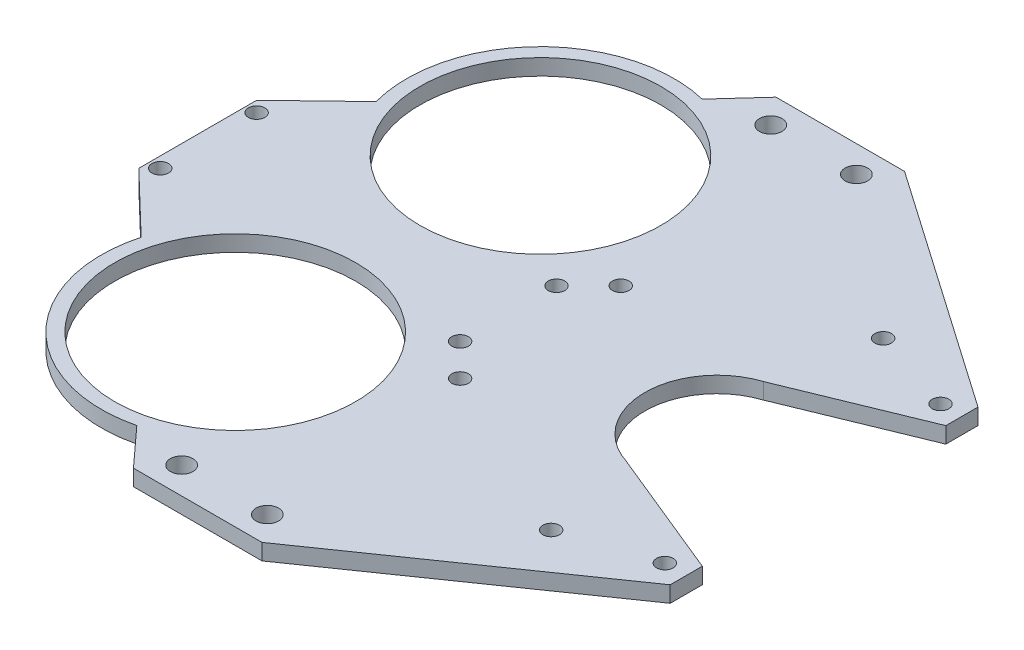
SolidWorks part; units mm, degrees
ref_plane "前视基准面" through (0, 0, 0) normal (0, 0, 1) x (1, 0, 0)
ref_plane "上视基准面" through (0, 0, 0) normal (0, 1, 0) x (1, 0, 0)
ref_plane "右视基准面" through (0, 0, 0) normal (1, 0, 0) x (0, 0, -1)
sketch "草图1" plane through (0, 0, 0) normal (0, 1, 0) x (1, 0, 0)
  line L0 (-55, 11) -> (-55, -11)
  line L1 (-55, 0) -> (5.5, 0) construction
  line L2 (-19.5, 28.5) -> (-19.5, -28.5) construction
  line L3 (-55, -11) -> (-27.8194, -37.148)
  line L4 (28.5, 0) -> (83.1006, 0) construction
  line L5 (-55, 11) -> (-27.8194, 37.148)
  line L6 (14, 12.5399) -> (14, 16.5)
  line L7 (-19.5, 40.5) -> (45.0428, 34.8675)
  line L8 (19, 21.5) -> (69.6179, 21.5)
  line L9 (14, -12.5399) -> (14, -16.5)
  line L13 (19, -21.5) -> (69.6179, -21.5)
  line L15 (-19.5, -40.5) -> (45.0428, -34.8675)
  circle A0 centre (0, 0) radius 1.55
  circle A1 centre (-27.5, 0) radius 1.55
  circle A2 centre (-46.5, 0) radius 1.55
  circle A3 centre (-19.5, -28.5) radius 4
  circle A4 centre (-19.5, -28.5) radius 8 construction
  circle A5 centre (-19.5, -28.5) radius 9.5 construction
  circle A6 centre (-19.5, -20.5) radius 1.55
  circle A7 centre (-19.5, -36.5) radius 1.55
  circle A8 centre (-10, -28.5) radius 1.55
  circle A9 centre (-29, -28.5) radius 1.55
  circle A10 centre (-29, 28.5) radius 1.55
  circle A11 centre (-10, 28.5) radius 1.55
  circle A12 centre (-19.5, 36.5) radius 1.55
  circle A13 centre (-19.5, 20.5) radius 1.55
  circle A14 centre (-19.5, 28.5) radius 4
  arc A15 (-27.8194, -37.148) -> (-17.4214, -40.3186) centre (-19.5, -28.5) ccw
  arc A16 (45.0428, -34.8675) -> (69.6179, -21.5) centre (42, 0) ccw
  arc A17 (-27.8194, 37.148) -> (-17.4214, 40.3186) centre (-19.5, 28.5) cw
  arc A18 (14, 16.5) -> (19, 21.5) centre (19, 16.5) cw
  arc A19 (45.0428, 34.8675) -> (69.6179, 21.5) centre (42, 0) cw
  arc A22 (14, 12.5399) -> (14, -12.5399) centre (19, 0) ccw
  arc A23 (14, -16.5) -> (19, -21.5) centre (19, -16.5) ccw
  point P10 (-55, 0)
  point P15 (-19.5, 0)
  dimension "D1" = 3.1
  dimension "D2" = 3.1
  dimension "D3" = 3.1
  dimension "D9" = 19
  dimension "D10" = 16
  dimension "D11" = 8
  dimension "D12" = 3.1
  dimension "D13" = 3.1
  dimension "D14" = 3.1
  dimension "D15" = 3.1
  dimension "D16" = 24
  dimension "D18" = 70
  dimension "D4" = 27.5
  dimension "D5" = 19
  dimension "D6" = 8.5
  dimension "D7" = 19.5
  dimension "D8" = 57
  dimension "D17" = 22
  dimension "D19" = 42
extrude "凸台-拉伸1" add sketch "草图1" along normal blind 3 contours A23 L9 A22 L6 A18 L8 A19 L7 A17 L5 L0 L3 A15 L15 A16 L13 A13 A11 A0 A1 A2 A3 A6 A7 A8 A9 A10 A12 A14 region at (-3.8495, 0, 0)
sketch "草图2" plane through (0, 3, 0) normal (0, 1, 0) x (1, 0, 0)
  line L0 (0, 0) -> (23.4042, 0) construction
  line L1 (5, 38.3619) -> (5, 57.5706) construction
  line L2 (-16.1256, 50) -> (-7, 50) construction
  line L3 (-7, 60) -> (-28.364, 36.5889)
  line L4 (17, 60) -> (-7, 60)
  line L5 (17, 60) -> (17, 50)
  line L6 (-17.4214, 40.3186) -> (-19.6569, 39.1776)
  line L7 (-19.6569, 39.1776) -> (-24.7059, 39.3119)
  line L8 (17, 60) -> (-7, 50) construction
  line L9 (17, 50) -> (-7, 60) construction
  line L10 (17, 37.3147) -> (17, 50)
  line L11 (-19.5, 40.5) -> (45.0428, 34.8675) construction
  line L12 (-17.4214, 40.3186) -> (17, 37.3147)
  line L13 (-3, 55) -> (13, 55) construction
  arc A1 (-24.7059, 39.3119) -> (-28.364, 36.5889) centre (-19.5, 28.5) ccw
  circle A2 centre (13, 55) radius 2.1
  circle A3 centre (-3, 55) radius 2.1
  point P10 (5, 55)
  dimension "D5" = 4.2
  dimension "D6" = 4.2
  dimension "D9" = 4
  dimension "D1" = 5
  dimension "D3" = 24
  dimension "D4" = 10
extrude "凸台-拉伸3" add sketch "草图2" against normal blind 3
fillet "圆角1" radius 4 1 edges at (17, 1.5, -37.3147)
fillet "圆角2" radius 314 1 edges at (-28.1008, 1.5, -36.8773) type face fillet first side face at (-41.5504, 1.5, -23.9386) second side face at (-17.5504, 1.5, -48.4386)
mirror "镜向2" about plane through (0, 0, 0) normal (0, 0, 1) of "凸台-拉伸3"
fillet "圆角3" radius 314 1 edges at (-28.1008, 1.5, 36.8773) type face fillet first side face at (-41.5504, 1.5, 23.9386) second side face at (-17.5504, 1.5, 48.4386)
fillet "圆角4" radius 4 1 edges at (17, 1.5, 37.3147)
sketch "草图3" plane through (0, 0, 0) normal (0, -1, 0) x (1, 0, 0)
  line L0 (-19.5, 28.5) -> (-10.1874, 19.4294) construction
  arc A1 (-8.6867, 48.2313) -> (-38.9114, 17.1226) centre (-19.5, 28.5) ccw
  arc A8 (-38.9114, 17.1226) -> (-30.7155, 21.9264) centre (-34.8135, 19.5245) ccw
  arc A9 (-13.2523, 39.9003) -> (-8.6867, 48.2313) centre (-10.9695, 44.0658) ccw
  arc A13 (-13.2523, 39.9003) -> (-30.7155, 21.9264) centre (-19.5, 28.5) ccw
  point P16 (-19.5, 28.5)
extrude "切除-拉伸2" cut sketch "草图3" against normal blind 3
sketch "草图4" plane through (0, 0, 0) normal (0, -1, 0) x (1, 0, 0)
  line L0 (-43.6248, 21.943) -> (-41.5357, 23.9528)
  line L1 (-55, 11) -> (-41.5357, 23.9528) construction
  line L2 (-15.5344, 50.6478) -> (-13.5804, 52.7891)
  line L3 (-7, 60) -> (-15.5344, 50.6478) construction
  arc A0 (-25.1183, 40.2233) -> (-31.3671, 33.8077) centre (-19.5, 28.5) ccw
  arc A1 (-15.5344, 50.6478) -> (-41.5357, 23.9528) centre (-19.5, 28.5) ccw
  arc A2 (-13.5804, 52.7891) -> (-43.6248, 21.943) centre (-19.5, 28.5) ccw
  arc A3 (-31.3671, 33.8077) -> (-25.1183, 40.2233) centre (-253.1548, 256.0828) ccw construction
  arc A4 (-31.3671, 33.8077) -> (-25.1183, 40.2233) centre (-253.1548, 256.0828) ccw
  circle A5 centre (-19.5, 28.5) radius 25 construction
  circle A6 centre (-19.5, 28.5) radius 22.5 construction
  dimension "D1" = 2.5
extrude "凸台-拉伸4" add sketch "草图4" against normal blind 3
mirror "镜向9" about plane through (0, 0, 0) normal (0, 0, 1) of "切除-拉伸2", "凸台-拉伸4"
sketch "草图5" plane through (0, 3, 0) normal (0, 1, 0) x (1, 0, 0)
  circle A0 centre (-19.5, 28.5) radius 22.5
  circle A1 centre (-19.5, -28.5) radius 22.5
extrude "切除-拉伸3" cut sketch "草图5" against normal blind 10
sketch "草图6" plane through (0, 3, 0) normal (0, 1, 0) x (1, 0, 0)
  arc A0 (7.8315, -7.5839) -> (7.8315, 7.5839) centre (42, 0) ccw
  arc A2 (14, 12.5399) -> (14, -12.5399) centre (19, 0) ccw construction
  arc A3 (7.8315, 7.5839) -> (7.8315, -7.5839) centre (19, 0) ccw
  circle A4 centre (42, 0) radius 13.5
extrude "凸台-拉伸5" add sketch "草图6" against normal blind 3
sketch "草图7" plane through (0, 3, 0) normal (0, 1, 0) x (1, 0, 0)
  line L0 (17, 60) -> (61.9755, 28.7398)
  line L1 (17, -60) -> (61.9756, -28.7398)
  line L2 (17, -40.9809) -> (17, -60) construction
  line L3 (20.6522, -36.996) -> (45.0428, -34.8675) construction
  line L4 (20.6522, 36.996) -> (45.0428, 34.8675) construction
  line L5 (17, 40.9809) -> (17, 60) construction
  line L6 (17, -40.9809) -> (17, -60)
  line L7 (20.6522, -36.996) -> (45.0428, -34.8675)
  line L8 (20.6522, 36.996) -> (45.0428, 34.8675)
  line L9 (17, 40.9809) -> (17, 60)
  arc A0 (45.0428, -34.8675) -> (45.0428, 34.8675) centre (42, 0) ccw construction
  arc A1 (20.6522, -36.996) -> (17, -40.9809) centre (21, -40.9809) ccw construction
  arc A2 (17, 40.9809) -> (20.6522, 36.996) centre (21, 40.9809) ccw construction
  arc A3 (20.6522, -36.996) -> (17, -40.9809) centre (21, -40.9809) ccw
  arc A4 (45.0428, -34.8675) -> (61.9756, -28.7398) centre (42, 0) ccw
  arc A5 (17, 40.9809) -> (20.6522, 36.996) centre (21, 40.9809) ccw
  arc A6 (61.9755, 28.7398) -> (45.0428, 34.8675) centre (42, 0) ccw
extrude "凸台-拉伸6" add sketch "草图7" against normal blind 3
sketch "草图8" plane through (0, 3, 0) normal (0, 1, 0) x (1, 0, 0)
  line L2 (61.9755, 28.7398) -> (61.9755, 22.7398)
  line L3 (61.9755, 22.7398) -> (35.9638, 12.0754)
  line L4 (42, 0) -> (71.6805, 0) construction
  line L5 (61.9755, -28.7398) -> (61.9755, -22.7398)
  line L6 (61.9755, -22.7398) -> (35.9638, -12.0754)
  line L7 (35.9638, 12.0754) -> (35.9638, -12.0754)
  arc A0 (61.9756, -28.7398) -> (61.9755, 28.7398) centre (42, 0) ccw construction
  arc A1 (61.9756, -28.7398) -> (61.9755, 28.7398) centre (42, 0) ccw
  circle A3 centre (42, 0) radius 13.5 construction
  dimension "D1" = 6
extrude "切除-拉伸5" cut sketch "草图8" against normal blind 3 and the other way through all
sketch "草图9" plane through (0, 3, 0) normal (0, 1, 0) x (1, 0, 0)
  line L0 (-55, 0) -> (-7.2883, 0) construction
  line L1 (-55, 11) -> (-55, -11) construction
  line L3 (3, -9) -> (-53, -9) construction
  line L4 (3, -9) -> (3, 9) construction
  line L5 (3, 9) -> (-53, 9) construction
  line L6 (-53, -9) -> (-53, 9) construction
  line L7 (3, -9) -> (-53, 9) construction
  line L8 (3, 9) -> (-53, -9) construction
  circle A0 centre (-53, -9) radius 1.55
  circle A1 centre (-53, 9) radius 1.55
  circle A2 centre (3, 9) radius 1.55
  circle A3 centre (3, -9) radius 1.55
  point P5 (-25, 0)
  dimension "D4" = 3.1
  dimension "D5" = 3.1
  dimension "D6" = 3.1
  dimension "D7" = 3.1
  dimension "D1" = 2
  dimension "D2" = 56
  dimension "D3" = 2
extrude "切除-拉伸7" cut sketch "草图9" against normal blind 10
sketch "草图10" plane through (0, 3, 0) normal (0, 1, 0) x (1, 0, 0)
  line L1 (-49.9835, 3.9667) -> (14.5357, 3.9667)
  line L2 (-49.9835, 3.9667) -> (-49.9835, -3.0749)
  line L3 (-49.9835, -3.0749) -> (14.5357, -3.0749)
  line L4 (14.5357, 3.9667) -> (14.5357, -3.0749)
  line L5 (-49.9835, 3.9667) -> (14.5357, -3.0749) construction
  line L6 (-49.9835, -3.0749) -> (14.5357, 3.9667) construction
  point P0 (-17.9847, 0)
extrude "凸台-拉伸7" add sketch "草图10" against normal blind 3
sketch "草图11" plane through (0, 3, 0) normal (0, 1, 0) x (1, 0, 0)
  line L0 (61.9755, 28.7398) -> (61.9755, 22.7398) construction
  line L1 (61.9755, 25.7398) -> (57.9755, 25.7398) construction
  line L2 (57.9755, 25.7398) -> (30.9824, 25.7398) construction
  line L3 (42, 0) -> (42, 35) construction
  line L4 (0, 0) -> (42.4289, 0) construction
  line L5 (5, 11) -> (12.4755, 11) construction
  line L6 (-0.6198, -11) -> (5, -11) construction
  line L7 (-0.6198, -11) -> (-0.6198, 11) construction
  line L8 (-0.6198, 11) -> (5, 11) construction
  line L9 (5, -11) -> (5, 11) construction
  line L10 (-0.6198, -11) -> (5, 11) construction
  line L11 (-0.6198, 11) -> (5, -11) construction
  line L12 (5, 11) -> (5, 17.3932) construction
  circle A0 centre (42, 0) radius 35 construction
  circle A1 centre (57.9755, 25.7398) radius 4 construction
  circle A2 centre (57.9755, 25.7398) radius 1.55
  circle A3 centre (42, 31) radius 4 construction
  circle A4 centre (42, 31) radius 1.55
  circle A5 centre (3, 9) radius 1.55 construction
  circle A6 centre (9, 15) radius 4 construction
  circle A7 centre (9, 15) radius 1.55
  point P17 (2.1901, 0)
  dimension "D1" = 70
  dimension "D2" = 8
  dimension "D3" = 3.1
  dimension "D4" = 8
  dimension "D5" = 3.1
  dimension "D6" = 2
  dimension "D8" = 8
  dimension "D9" = 3.1
  dimension "D7" = 2
  dimension "D10" = 19.9755
  dimension "D11" = 25.7398
extrude "切除-拉伸8" cut sketch "草图11" against normal blind 10
mirror "镜向10" about plane through (0, 0, 0) normal (0, 0, 1) of "切除-拉伸8"
